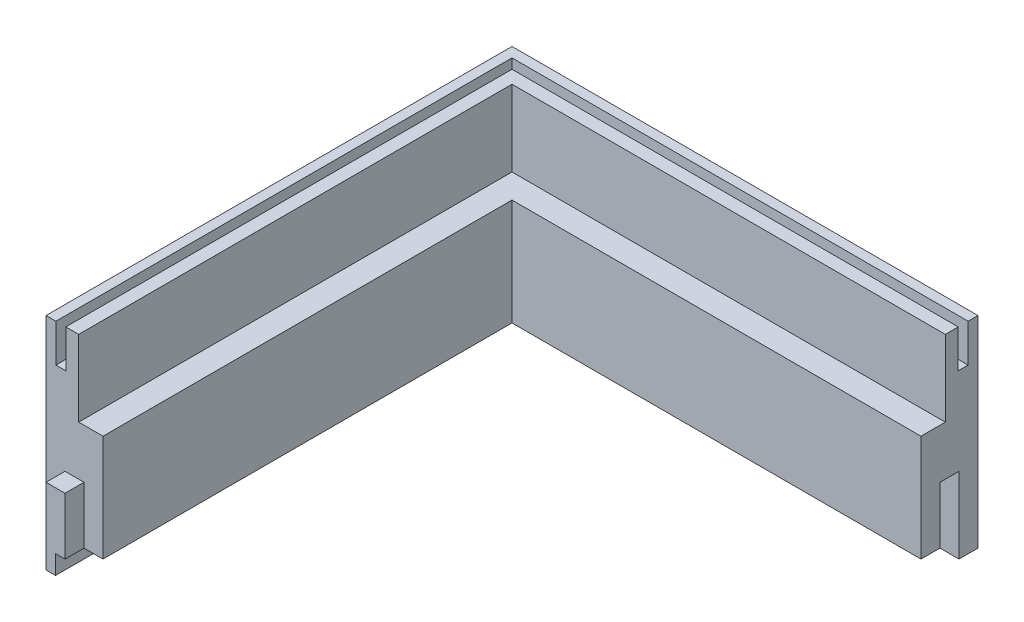
SolidWorks part; units mm, degrees
ref_plane "Front Plane" through (0, 0, 0) normal (0, 0, 1) x (1, 0, 0)
ref_plane "Top Plane" through (0, 0, 0) normal (0, 1, 0) x (1, 0, 0)
ref_plane "Right Plane" through (0, 0, 0) normal (1, 0, 0) x (0, 0, -1)
sketch "Sketch1" plane through (0, 0, 0) normal (0, 1, 0) x (1, 0, 0)
  line L7 (-60.6056, 37.6635) -> (95.0964, 37.6635)
  line L12 (95.0964, 37.6635) -> (95.0964, 18.6135)
  line L13 (95.0964, 18.6135) -> (-41.5556, 18.6135)
  line L14 (-41.5556, 18.6135) -> (-41.5556, -118.0385)
  line L15 (-41.5556, -118.0385) -> (-60.6056, -118.0385)
  line L16 (-60.6056, -118.0385) -> (-60.6056, 37.6635)
  line L17 (-57.3036, -118.0385) -> (-57.3036, 34.3615)
  line L18 (-57.3036, 34.3615) -> (95.0964, 34.3615)
  line L19 (-54.0016, -118.0385) -> (-54.0016, 31.0595)
  line L20 (-54.0016, 31.0595) -> (95.0964, 31.0595)
  line L21 (95.0964, 27.7575) -> (-50.6996, 27.7575)
  line L22 (-50.6996, 27.7575) -> (-50.6996, -118.0385)
  dimension "D1" = 155.702
  dimension "D2" = 19.05
  dimension "D3" = 3.302
  dimension "D4" = 3.302
  dimension "D5" = 3.302
extrude "Boss-Extrude5" add sketch "Sketch1" along normal blind 67.31 contours L14 L15 L16 L7 L12 L13
sketch "Sketch8" plane through (0, 67.31, 0) normal (0, 1, 0) x (1, 0, 0)
  line L0 (-57.3036, -118.0385) -> (-57.3036, 34.3615)
  line L1 (-57.3036, -118.0385) -> (-54.0016, -118.0385)
  line L2 (95.0964, 34.3615) -> (95.0964, 31.0595)
  line L3 (-41.5556, -118.0385) -> (-60.6056, -118.0385) construction
  line L4 (-57.3036, 34.3615) -> (95.0964, 34.3615)
  line L5 (95.0964, 37.6635) -> (95.0964, 18.6135) construction
  line L6 (-60.6056, -118.0385) -> (-60.6056, 37.6635) construction
  line L7 (-54.0016, -118.0385) -> (-54.0016, 31.0595)
  line L8 (-54.0016, 31.0595) -> (95.0964, 31.0595)
  dimension "D1" = 3.302
  dimension "D2" = 3.302
extrude "Cut-Extrude2" cut sketch "Sketch8" against normal blind 12.6933
sketch "Sketch9" plane through (0, 67.31, 0) normal (0, 1, 0) x (1, 0, 0)
  line L0 (-49.6836, -118.0385) -> (-49.6836, 26.7415)
  line L1 (-41.5556, -118.0385) -> (-54.0016, -118.0385) construction
  line L2 (-49.6836, 26.7415) -> (95.0964, 26.7415)
  line L3 (95.0964, 31.0595) -> (95.0964, 18.6135) construction
  line L4 (95.0964, 26.7415) -> (95.0964, 18.6135)
  line L5 (95.0964, 18.6135) -> (-41.5556, 18.6135)
  line L6 (-41.5556, 18.6135) -> (-41.5556, -118.0385)
  line L7 (-41.5556, -118.0385) -> (-49.6836, -118.0385)
  dimension "D1" = 4.318
extrude "Cut-Extrude3" cut sketch "Sketch9" against normal blind 25.4
sketch "Sketch11" plane through (0, 0, 118.0385) normal (0, 0, 1) x (1, 0, 0)
  line L0 (-41.5556, 0) -> (-60.6056, 0) construction
  line L1 (-54.2556, 0) -> (-47.9056, 0)
  line L2 (-54.2556, 0) -> (-54.2556, 25.4)
  line L3 (-54.2556, 25.4) -> (-47.9056, 25.4)
  line L4 (-47.9056, 0) -> (-47.9056, 25.4)
  dimension "D1" = 6.35
  dimension "D2" = 6.35
  dimension "D3" = 25.4
extrude "Boss-Extrude6" add sketch "Sketch11" along normal blind 6.35
sketch "Sketch12" plane through (95.0964, 0, 0) normal (1, 0, 0) x (0, 0, -1)
  line L0 (37.6635, 0) -> (18.6135, 0) construction
  line L1 (24.9635, 0) -> (31.3135, 0)
  line L2 (24.9635, 0) -> (24.9635, 25.4)
  line L3 (24.9635, 25.4) -> (31.3135, 25.4)
  line L4 (31.3135, 0) -> (31.3135, 25.4)
  dimension "D1" = 6.35
  dimension "D2" = 6.35
  dimension "D3" = 25.4
extrude "Cut-Extrude4" cut sketch "Sketch12" against normal blind 6.35
sketch "Sketch13" plane through (0, 0, 0) normal (0, -1, 0) x (1, 0, 0)
  line L4 (-51.0806, 124.3885) -> (-51.0806, -25.3997)
  line L5 (-54.2556, 124.3885) -> (-47.9056, 124.3885) construction
  line L6 (88.7464, -28.1385) -> (-51.0806, -28.1385)
  line L7 (88.7464, -24.9635) -> (88.7464, -31.3135) construction
  line L8 (-51.0806, -28.1385) -> (-51.0806, -25.3997)
extrude "Cut-Extrude5" cut sketch "Sketch13" against normal blind 6.35 and the other way through all
